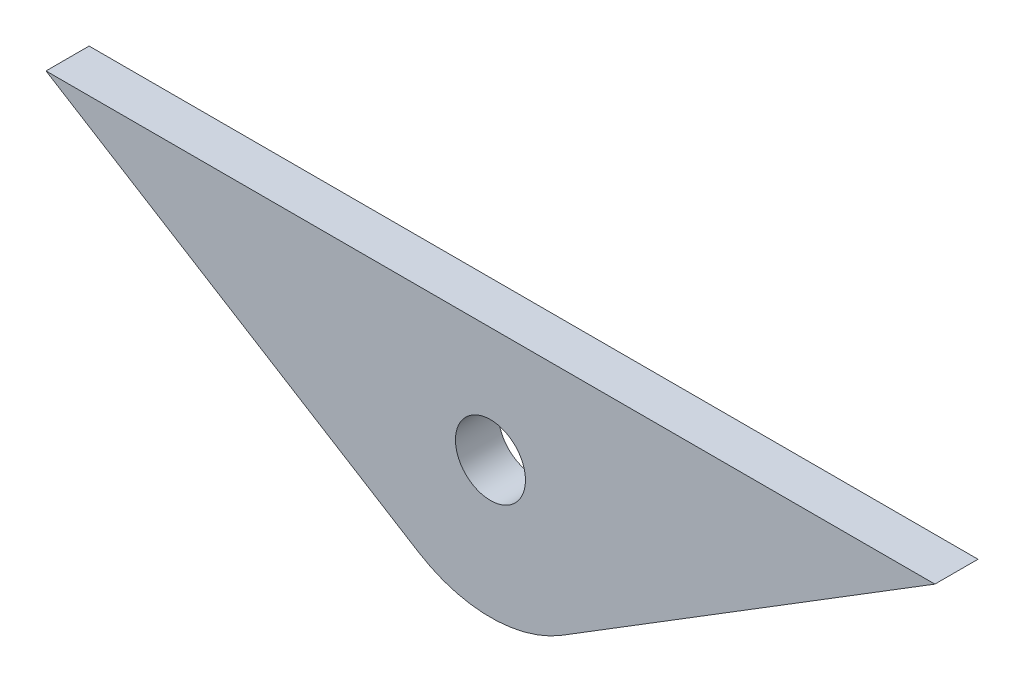
SolidWorks part; units mm, degrees
material "AISI 1020"
ref_plane "Спереди" through (0, 0, 0) normal (0, 0, 1) x (1, 0, 0)
ref_plane "Сверху" through (0, 0, 0) normal (0, 1, 0) x (1, 0, 0)
ref_plane "Справа" through (0, 0, 0) normal (1, 0, 0) x (0, 0, -1)
sketch "Эскиз1" plane through (0, 0, 0) normal (0, 0, 1) x (1, 0, 0)
  line L0 (-82.5017, 0) -> (-47.9073, -21.407) construction
  line L1 (-34.5944, -21.407) -> (0, 0) construction
  line L2 (-82.5017, 0) -> (-47.9073, -21.407)
  line L3 (-34.5944, -21.407) -> (0, 0)
  line L4 (-82.5017, 0) -> (0, 0)
  arc A0 (-47.9073, -21.407) -> (-34.5944, -21.407) centre (-41.2508, -10.65) ccw construction
  arc A1 (-47.9073, -21.407) -> (-34.5944, -21.407) centre (-41.2508, -10.65) ccw
  circle A2 centre (-41.2508, -10.65) radius 3.25
  dimension "D1" = 6.5
base flange "Базовая кромка1" sketch "Эскиз1" thickness 4 reverse thickness direction no parameters "D1"=0.74
sketch "Сгиб-Линии1" [suppressed] plane through (0, 0, 0) normal (0, 1, 0) x (1, 0, 0)
sketch "Граничная рамка1" [suppressed] plane through (0, 0, 0) normal (0, 1, 0) x (1, 0, 0)
sheet metal parameters "Листовой металл3" thickness 4 parameters "D1"=0.74
flat pattern "Развертка3" [suppressed]
sketch "Сгиб-Линии2" plane through (0, 0, 0) normal (0, 1, 0) x (1, 0, 0)
sketch3d "Граничная рамка2" [suppressed]
  line L0 (-41.2508, -12.65, 0) -> (41.2508, -12.65, 0) construction
  line L1 (-41.2508, 10.65, 0) -> (41.2508, 10.65, 0) construction
  line L2 (-41.2508, -12.65, 0) -> (-41.2508, 10.65, 0) construction
  line L3 (41.2508, -12.65, 0) -> (41.2508, 10.65, 0) construction
